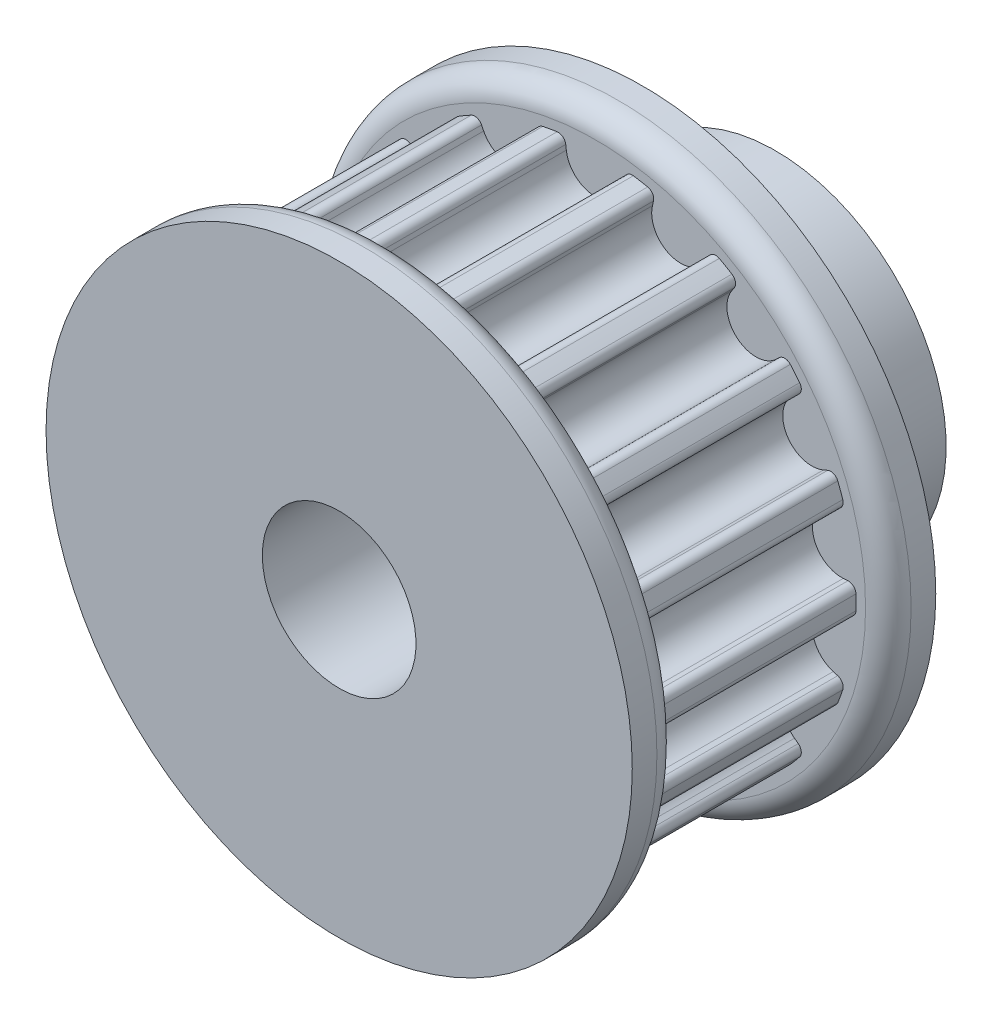
SolidWorks part; units mm, degrees
material "6061 합금"
ref_plane "정면" through (0, 0, 0) normal (0, 0, 1) x (1, 0, 0)
ref_plane "윗면" through (0, 0, 0) normal (0, 1, 0) x (1, 0, 0)
ref_plane "우측면" through (0, 0, 0) normal (1, 0, 0) x (0, 0, -1)
sketch "스케치3" plane through (0, 0, 0) normal (0, 0, 1) x (1, 0, 0)
  line L0 (0, 0) -> (0, 13.7524) construction
  line L1 (0, 0) -> (-4.8991, 13.4601) construction
  line L2 (0, 13.7524) -> (0, 15.4524) construction
  line L3 (-1.5246, 13.0088) -> (-1.6008, 13.659)
  line L4 (1.5246, 13.0088) -> (1.6008, 13.659)
  circle A0 centre (0, 0) radius 14.3239 construction
  circle A1 centre (0, 0) radius 15.4524 construction
  circle A2 centre (0, 0) radius 13.7524
  circle A3 centre (0, 13.1874) radius 1.535
  dimension "D2" = 28.6479
  dimension "D5" = 3.07
  dimension "D3" = 27.5049
  dimension "D1" = 20
  dimension "D4" = 2.1
  dimension "D6" = 3.8
extrude "보스-돌출2" add sketch "스케치3" along normal mid plane 11 contours A2
extrude "컷-돌출2" cut sketch "스케치3<3>" against normal through all both and the other way through all contours A3 A2 L3 | A2 A3 | A3 L4 A2 region at (0, 12.8159, 0) region at (-1.5387, 13.5029, 0) region at (1.5387, 13.5029, 0)
sketch "스케치3<3>" plane through (0, 0, 0) normal (0, 0, 1) x (1, 0, 0) same geometry as "스케치3"
fillet "필렛1" radius 0.4 2 edges at (1.6008, 13.659, 0) (-1.6008, 13.659, 0)
pattern_circular "원형 패턴1" count 18 over 360 about axis through (0, 0, 5.5) along (0, 0, -1) of "컷-돌출2", "필렛1"
sketch "스케치12" plane through (0, 0, 5.5) normal (0, 0, 1) x (1, 0, 0)
  circle A0 centre (0, 0) radius 15.4524 construction
  circle A1 centre (0, 0) radius 15.4524
extrude "보스-돌출4" add sketch "스케치12" along normal blind 2.5
sketch "스케치13" plane through (0, 0, -5.5) normal (0, 0, -1) x (-1, 0, 0)
  circle A0 centre (0, 0) radius 15.4524 construction
  circle A1 centre (0, 0) radius 15.4524
extrude "보스-돌출5" add sketch "스케치13" along normal blind 2.5
fillet "필렛2" radius 1.2 2 edges at (15.4524, 0, 5.5) (-15.4524, 0, -5.5)
sketch "스케치5" plane through (0, 0, -8) normal (0, 0, -1) x (-1, 0, 0)
  circle A2 centre (0, 0) radius 9
  dimension "D1" = 18
extrude "보스-돌출3" add sketch "스케치5" along normal blind 7
sketch "스케치4" plane through (0, 0, 8) normal (0, 0, -1) x (-1, 0, 0)
  circle A0 centre (0, 0) radius 4.05
  dimension "D1" = 8.1
extrude "컷-돌출3" cut sketch "스케치4" along normal through all
hole_wizard "M3x0.5 탭을 위한 탭 드릴1" positions "스케치7" profile "스케치8" hole size "M3x0.5" standard "Ansi Metric" end condition through all
sketch "스케치7" plane through (0, 0, 0) normal (0, 1, 0) x (1, 0, 0)
  line L0 (0, 15) -> (0, 8) construction
  line L1 (9, 15) -> (-9, 15) construction
  line L4 (9, 8) -> (-9, 8) construction
  point P0 (0, 11.5)
sketch "스케치8" plane through (0, 0, -11.5) normal (1, 0, 0) x (0, 0, -1)
  line L0 (0, 0) -> (0, 15.4524)
  line L1 (0, 15.4524) -> (1.2, 15.4524)
  line L2 (1.2, 15.4524) -> (1.2, 0)
  line L5 (1.2, 0) -> (0, 0)
  line L11 (0, -6.35) -> (0, 107.95) construction
  dimension "관통 구멍 지름" = 2.4
  dimension "관통 구멍 깊이" = 15.4524
sketch "스케치14" plane through (0, 0, 8) normal (0, 0, 1) x (1, 0, 0)
  circle A0 centre (0, 0) radius 16
  circle A1 centre (0, 0) radius 18.5
  dimension "D1" = 2.5
  dimension "D2" = 32
extrude "보스-돌출6" [suppressed] add sketch "스케치14" against normal up to surface (13 mm away) separate body up to face at (-9, 0, -8)
equation "\"n\"= 18'number of teeth"
equation "\"D2@스케치3\"=5*\"n\"/(PI)"
equation "\"D1@스케치3\"=360/\"n\""
equation "\"D1@원형 패턴1\"=\"n\""
equation "\"D3@스케치3\"=\"D2@스케치3\"-2*0.225*2.54"
